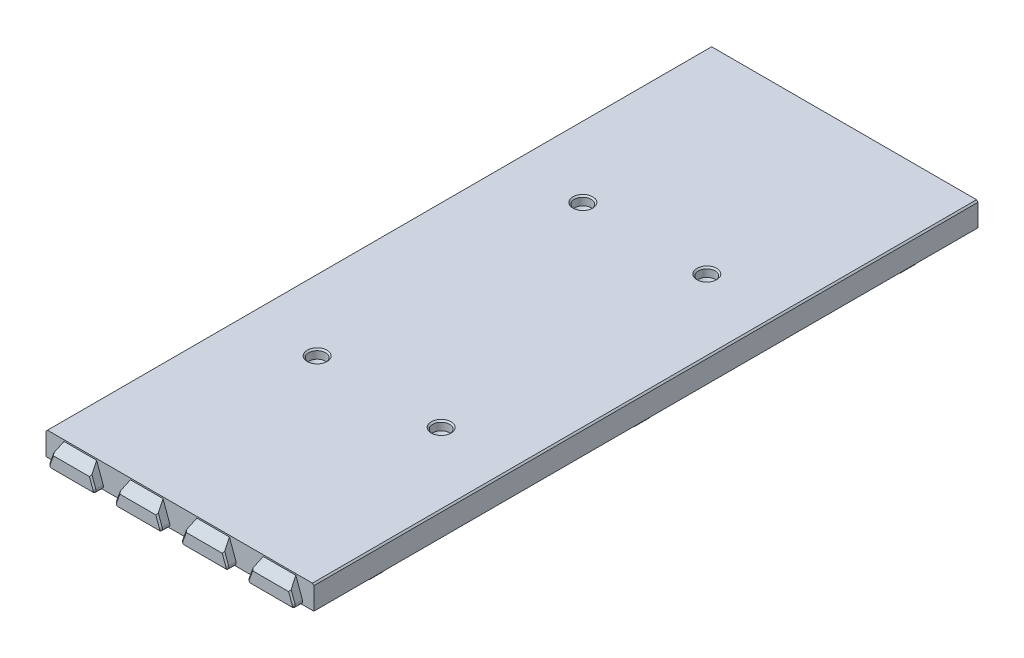
SolidWorks part; units mm, degrees
ref_plane "Front Plane" through (0, 0, 0) normal (0, 0, 1) x (1, 0, 0)
ref_plane "Top Plane" through (0, 0, 0) normal (0, 1, 0) x (1, 0, 0)
ref_plane "Right Plane" through (0, 0, 0) normal (1, 0, 0) x (0, 0, -1)
sketch "Sketch1" plane through (0, 0, 0) normal (0, 0, 1) x (1, 0, 0)
  line L0 (0, 0) -> (0, 8) construction
  line L1 (-45.375, 0) -> (0, 0) construction
  line L2 (-45.375, 0) -> (-45.375, 8)
  line L3 (-45.375, 8) -> (45.375, 8)
  line L5 (-45.375, 0) -> (-43.375, 0)
  line L6 (-43.375, 0) -> (-43.375, 6)
  line L7 (-43.375, 6) -> (43.375, 6)
  line L9 (43.375, 0) -> (43.375, 6)
  line L10 (45.375, 0) -> (43.375, 0)
  line L11 (45.375, 0) -> (45.375, 8)
  point P8 (0, 6)
  dimension "D2" = 6
  dimension "D1" = 45.375
  dimension "D3" = 2
  dimension "D4" = 2
extrude "Boss-Extrude1" add sketch "Sketch1" against normal blind 112.5
sketch "Sketch7" plane through (0, 0, 0) normal (0, 0, 1) x (1, 0, 0)
  line L2 (-43.375, 0) -> (43.375, 0)
  line L13 (-43.375, 0) -> (-43.375, 6)
  line L15 (-43.375, 6) -> (43.375, 6)
  line L16 (43.375, 0) -> (43.375, 6)
  line M3 (-43.375, 0) -> (-43.375, 6)
  line M4 (-43.375, 6) -> (43.375, 6)
  line M5 (43.375, 6) -> (43.375, 0)
extrude "Boss-Extrude7" add sketch "Sketch7" against normal blind 1 contours M4 M3 | M5 region at (0, 3, 0)
sketch "Sketch2" plane through (0, 0, 0) normal (0, 0, 1) x (1, 0, 0)
  line L14 (28.4118, 8) -> (25.5, 0)
  line L15 (45.375, 8) -> (-45.375, 8) construction
  line L16 (-45.375, 0) -> (45.375, 0) construction
  line L17 (25.5, 0) -> (42, 0)
  line L18 (28.4118, 8) -> (39.0882, 8)
  line L19 (-45.375, 0) -> (45.375, 0) construction
  line L21 (39.0882, 8) -> (42, 0)
  line L24 (22.5, 0) -> (22.5, 8) construction
  line L27 (5.9118, 8) -> (3, 0)
  line L28 (5.9118, 8) -> (16.5882, 8)
  line L29 (3, 0) -> (19.5, 0)
  line L30 (16.5882, 8) -> (19.5, 0)
  line L31 (-16.5882, 8) -> (-19.5, 0)
  line L32 (-16.5882, 8) -> (-5.9118, 8)
  line L33 (-19.5, 0) -> (-3, 0)
  line L34 (-5.9118, 8) -> (-3, 0)
  line L35 (-39.0882, 8) -> (-42, 0)
  line L36 (-39.0882, 8) -> (-28.4118, 8)
  line L37 (-42, 0) -> (-25.5, 0)
  line L38 (-28.4118, 8) -> (-25.5, 0)
  line L39 (28.4118, 8) -> (5.9118, 8) construction
  line L40 (45, 8) -> (45, 0) construction
  line L41 (45.375, 0) -> (45.375, 8) construction
  line L42 (-45, 8) -> (-45, 0) construction
  line L43 (-45.375, 8) -> (-45.375, 0) construction
  point P22 (33.75, 8)
  point P23 (11.25, 8)
  dimension "D1" = 70
  dimension "D2" = 0.375
  dimension "D3" = 3
  dimension "D4" = 3
  dimension "D5" = 70
  dimension "D7" = 22.5
  dimension "D8" = 22.5
  dimension "D9" = 0.375
  dimension "D10" = 3
  dimension "D11" = 8
  dimension "D6" = 4
extrude "Boss-Extrude4" add sketch "Sketch2" along normal blind 3
sketch "Sketch8" plane through (0, 0, 0) normal (0, -1, 0) x (1, 0, 0)
  line L0 (-45.375, -22.5) -> (45.375, -22.5) construction
  line L2 (45.375, -112.5) -> (45.375, 0) construction
  line L3 (-45.375, 0) -> (-42, 0) construction
  line L4 (-44, -24.9559) -> (-44, -20.0441)
  line L5 (-44, -20.0441) -> (-40, -21.5)
  line L6 (-40, -21.5) -> (-40, -23.5)
  line L7 (-44, -112.5) -> (-44, -110.0441)
  line L8 (-44, -110.0441) -> (-40, -111.5)
  line L9 (-40, -111.5) -> (-40, -112.5)
  line L10 (-43.375, -112.5) -> (43.375, -112.5) construction
  line L11 (-40, -112.5) -> (-44, -112.5)
  line L12 (-44, -24.9559) -> (-40, -23.5)
  line L13 (0, -112.5) -> (0, 0) construction
  line L23 (-45.375, -112.5) -> (-45.375, 0) construction
  line L24 (44, -24.9559) -> (40, -23.5)
  line L25 (40, -21.5) -> (40, -23.5)
  line L26 (44, -20.0441) -> (40, -21.5)
  line L27 (44, -24.9559) -> (44, -20.0441)
  line L28 (-45.375, -112.5) -> (-43.375, -112.5) construction
  line L29 (40, -112.5) -> (44, -112.5)
  line L30 (40, -111.5) -> (40, -112.5)
  line L31 (44, -110.0441) -> (40, -111.5)
  line L32 (44, -112.5) -> (44, -110.0441)
  point P19 (-40, -22.5)
  point P32 (40, -22.5)
  dimension "D1" = 22.5
  dimension "D2" = 1.375
  dimension "D3" = 70
  dimension "D4" = 4
  dimension "D6" = 4
  dimension "D7" = 70
  dimension "D8" = 1
  dimension "D9" = 1
extrude "Boss-Extrude8" add sketch "Sketch8" against normal up to next and the other way blind 2
chamfer "Chamfer4" distance 0.5 angle 45 14 edges at (-40, -2, -112) (-42, -2, -110.7721) (-44, -2, -111.2721) (-42, -2, -24.2279) (-40, -2, -22.5) (-42, -2, -20.7721) (40, -2, -22.5) (42, -2, -24.2279) (42, -2, -20.7721) (44, -2, -22.5) (40, -2, -112) (44, -2, -111.2721) (42, -2, -110.7721) (-44, -2, -22.5)
fillet "Fillet4" radius 1 8 edges at (-42, 0, 1.5) (-25.5, 0, 1.5) (-19.5, 0, 1.5) (-3, 0, 1.5) (3, 0, 1.5) (19.5, 0, 1.5) (25.5, 0, 1.5) (42, 0, 1.5)
chamfer "Chamfer6" distance 0.5 angle 45 20 edges at (27.2001, 4.671, 3) (40.2999, 4.671, 3) (33.75, 0, 3) (-40.2999, 4.671, 3) (-33.75, 0, 3) (-27.2001, 4.671, 3) (-17.7999, 4.671, 3) (-11.25, 0, 3) (-4.7001, 4.671, 3) (4.7001, 4.671, 3) (17.7999, 4.671, 3) (11.25, 0, 3) (-41.391, 0.4264, 3) (-26.109, 0.4264, 3) (-18.891, 0.4264, 3) (-3.609, 0.4264, 3) (3.609, 0.4264, 3) (18.891, 0.4264, 3) (26.109, 0.4264, 3) (41.391, 0.4264, 3)
fillet "Fillet2" radius 2 23 edges at (0, 6, -1) (-43.375, 3, -110.2716) (-41.6875, 6, -110.8858) (-40, 6, -112) (-43.375, 3, -1) (-41.6875, 6, -20.8858) (-43.375, 3, -20.2716) (-43.375, 6, -67.5) (-40, 6, -22.5) (-41.6875, 6, -24.1142) (-43.375, 3, -24.7284) (43.375, 6, -10.6358) (43.375, 3, -1) (-43.375, 6, -10.6358) (43.375, 3, -24.7284) (43.375, 3, -20.2716) (43.375, 3, -110.2716) (40, 6, -112) (41.6875, 6, -110.8858) (41.6875, 6, -20.8858) (40, 6, -22.5) (43.375, 6, -67.5) (41.6875, 6, -24.1142)
mirror "Mirror2" about plane through (0, 0, -112.5) normal (0, 0, 1) of "Fillet4", "Boss-Extrude1", "Boss-Extrude7", "Boss-Extrude4", "Boss-Extrude8", "Chamfer4", "Fillet2", "Chamfer6"
sketch "Sketch9" plane through (0, 0, 0) normal (0, 1, 0) x (1, 0, 0)
  line L16 (0, 112.5) -> (0, 0) construction
  line L17 (-45.375, 112.5) -> (45.375, 112.5) construction
  line L18 (-45.375, 115.4563) -> (-45.375, 109.5437) construction
  line L20 (45.375, 225) -> (45.375, 0) construction
  circle A0 centre (-21, 67.5) radius 5
  circle A4 centre (21, 67.5) radius 5
  circle A5 centre (21, 157.5) radius 5
  circle A6 centre (-21, 157.5) radius 5
  point P23 (0, 112.5)
  point P24 (0, 112.5)
  dimension "D3" = 10
  dimension "D1" = 45
  dimension "D2" = 21
extrude "Boss-Extrude9" add sketch "Sketch9" along normal up to next
fillet "Fillet3" radius 3 4 edges at (-21, 6, -72.5) (-21, 6, -162.5) (21, 6, -162.5) (21, 6, -72.5)
sketch "Sketch10" plane through (0, 0, 0) normal (0, 1, 0) x (1, 0, 0)
  circle A0 centre (-21, 157.5) radius 1.85
  circle A1 centre (-21, 67.5) radius 1.85
  circle A2 centre (21, 67.5) radius 1.85
  circle A3 centre (21, 157.5) radius 1.85
  dimension "D1" = 3.7
extrude "Cut-Extrude2" cut sketch "Sketch10" along normal through all
sketch "Sketch11" plane through (0, 8, 0) normal (0, 1, 0) x (1, 0, 0)
  circle A0 centre (-21, 157.5) radius 2.85
  circle A1 centre (21, 157.5) radius 2.85
  circle A2 centre (21, 67.5) radius 2.85
  circle A3 centre (-21, 67.5) radius 2.85
  dimension "D1" = 5.7
extrude "Cut-Extrude3" cut sketch "Sketch11" against normal blind 3
chamfer "Chamfer7" distance 1 angle 45 4 edges at (21, 5, -155.65) (-21, 5, -155.65) (21, 5, -65.65) (-21, 5, -65.65)
sketch "Sketch12" plane through (0, 0, 0) normal (1, 0, 0) x (0, 0, -1)
  line L0 (0, 7.5) -> (-3, 4.5)
  line L1 (-3, 1.171) -> (-3, 8) construction
  line L2 (-3, 4.5) -> (-3, 7.5)
  line L4 (112.5, 8) -> (112.5, 0) construction
  line L5 (225, 8) -> (0, 8) construction
  line L6 (225, 0) -> (0, 0) construction
  line L10 (0, 1.342) -> (0, 8) construction
  line L11 (-3, 7.5) -> (0, 7.5) construction
  line L12 (-3, 7.5) -> (-3, 8)
  line L13 (-3, 8) -> (0, 8)
  line L14 (0, 8) -> (0, 7.5)
  line L15 (228, 7.5) -> (225, 7.5) construction
  line L21 (225, 8) -> (225, 7.5)
  line L22 (228, 8) -> (225, 8)
  line L23 (228, 7.5) -> (228, 8)
  line L24 (228, 4.5) -> (228, 7.5)
  line L25 (225, 7.5) -> (228, 4.5)
  dimension "D1" = 0.5
  dimension "D2" = 3
  dimension "D3" = 45
extrude "Cut-Extrude4" cut sketch "Sketch12" against normal through all both and the other way through all
chamfer "Chamfer8" distance 0.5 angle 45 6 edges at (21, 8, -154.65) (-21, 8, -154.65) (45.375, 8, -112.5) (21, 8, -64.65) (-21, 8, -64.65) (-45.375, 8, -112.5)
